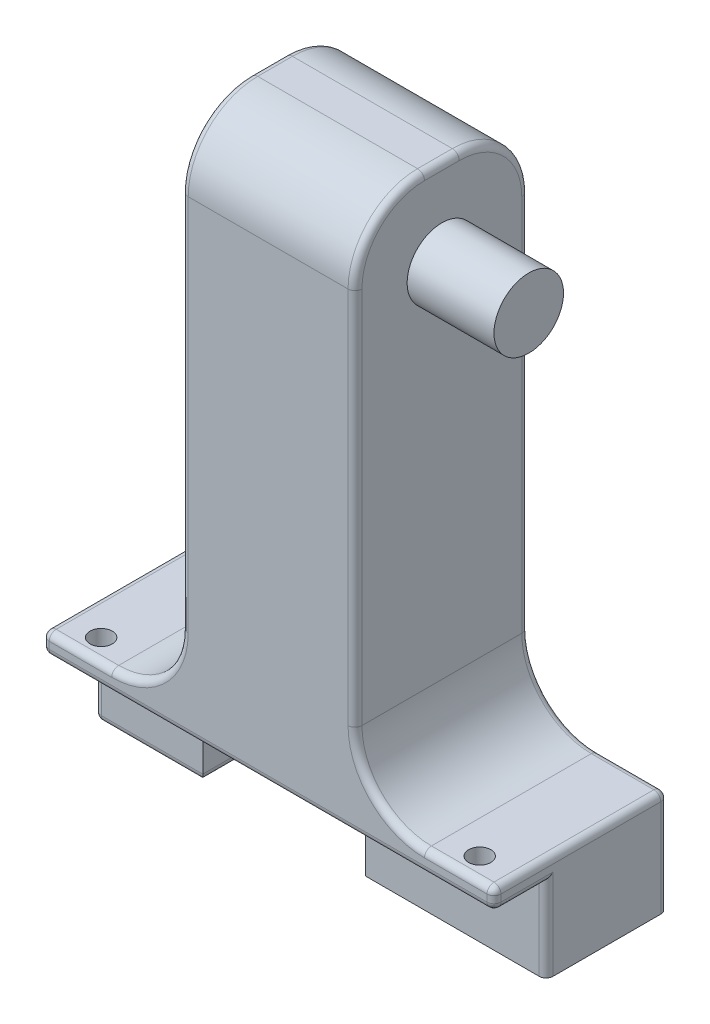
SolidWorks part; units mm, degrees
ref_plane "Front Plane" through (0, 0, 0) normal (0, 0, 1) x (1, 0, 0)
ref_plane "Top Plane" through (0, 0, 0) normal (0, 1, 0) x (1, 0, 0)
ref_plane "Right Plane" through (0, 0, 0) normal (1, 0, 0) x (0, 0, -1)
sketch "Sketch2" plane through (0, 0, 0) normal (0, 1, 0) x (1, 0, 0)
  line L1 (-32.5, -12.5) -> (32.5, -12.5)
  line L2 (-32.5, -12.5) -> (-32.5, 12.5)
  line L3 (-32.5, 12.5) -> (32.5, 12.5)
  line L4 (32.5, -12.5) -> (32.5, 12.5)
  line L5 (-32.5, -12.5) -> (32.5, 12.5) construction
  line L6 (-32.5, 12.5) -> (32.5, -12.5) construction
  point P0 (0, 0)
  dimension "D1" = 65
  dimension "D2" = 25
extrude "Boss-Extrude1" add sketch "Sketch2" along normal blind 3
sketch "Sketch3" plane through (0, 0, 0) normal (0, -1, 0) x (1, 0, 0)
  line L0 (32.5, -12.5) -> (-32.5, -12.5) construction
  line L1 (-32.5, 5) -> (-16.9, 5)
  line L2 (-32.5, 5) -> (-32.5, -12.5)
  line L3 (-32.5, -12.5) -> (-16.9, -12.5)
  line L4 (-16.9, 5) -> (-16.9, -12.5)
  line L10 (32.5, 5) -> (6.5, 5)
  line L12 (6.5, 5) -> (6.5, 0)
  line L13 (6.5, 0) -> (12.5, 0)
  line L14 (12.5, 0) -> (12.5, -12.5)
  line L15 (32.5, -12.5) -> (-32.5, -12.5) construction
  line L16 (12.5, -12.5) -> (32.5, -12.5)
  line L17 (32.5, -12.5) -> (32.5, 5)
  line L18 (-32.5, -12.5) -> (-32.5, 12.5) construction
  point P16 (0, 0)
  dimension "D1" = 15.6
  dimension "D2" = 26
  dimension "D3" = 20
  dimension "D4" = 17.5
extrude "Boss-Extrude2" add sketch "Sketch3" along normal blind 12
sketch "Sketch5" plane through (0, 3, 0) normal (0, 1, 0) x (1, 0, 0)
  circle A0 centre (27.2349, -9.2897) radius 1.6
  circle A1 centre (-27.2349, -9.2897) radius 1.6
  circle A2 centre (27.2349, -9.2897) radius 1.6 construction
extrude "Cut-Extrude1" cut sketch "Sketch5" against normal through all
sketch "Sketch6" plane through (0, 3, 0) normal (0, 1, 0) x (1, 0, 0)
  line L0 (-32.5, -12.5) -> (32.5, -12.5) construction
  line L1 (12.5, -12.5) -> (-12.5, -12.5)
  line L2 (12.5, -12.5) -> (12.5, 12.5)
  line L3 (12.5, 12.5) -> (-12.5, 12.5)
  line L4 (-12.5, -12.5) -> (-12.5, 12.5)
  line L5 (32.5, 12.5) -> (-32.5, 12.5) construction
  line L6 (0, -20.7065) -> (0, 20.7065) construction
  point P12 (0, 0)
  dimension "D1" = 25
extrude "Boss-Extrude3" add sketch "Sketch6" along normal blind 74.4
sketch "Sketch7" plane through (12.5, 0, 0) normal (1, 0, 0) x (0, 0, -1)
  line L0 (12.5, 77.4) -> (12.5, 3) construction
  line L1 (-12.5, 77.4) -> (12.5, 77.4) construction
  line L2 (-12.5, 77.4) -> (-12.5, 3) construction
  circle A0 centre (0, 64.9) radius 12.5
sketch "Sketch8" plane through (-12.5, 0, 0) normal (-1, 0, 0) x (0, 0, 1)
  circle A0 centre (0, 64.9) radius 12.5 construction
  circle A1 centre (0, 64.9) radius 12.5
ref_axis "Axis1" through (-18.9714, 64.9, 0) along (1, 0, 0)
fillet "Fillet1" radius 10 4 edges at (0, 77.4, 12.5) (0, 77.4, -12.5) (-12.5, 3, 0) (12.5, 3, 0)
fillet "Fillet2" radius 1 33 edges at (27.5, 3, 12.5) (15.4289, 5.9289, 12.5) (12.5, 40.2, 12.5) (12.5, 74.4711, 9.5711) (12.5, 77.4, 0) (12.5, 74.4711, -9.5711) (12.5, 40.2, -12.5) (15.4289, 5.9289, -12.5) (-27.5, 3, 12.5) (-15.4289, 5.9289, 12.5) (-12.5, 40.2, 12.5) (-12.5, 74.4711, 9.5711) (-12.5, 77.4, 0) (-12.5, 74.4711, -9.5711) (-27.5, 3, -12.5) (-15.4289, 5.9289, -12.5) (-24.7, -12, 5) (-16.9, -12, -3.75) (-24.7, -12, -12.5) (-32.5, -12, -3.75) (-32.5, 1.5, 12.5) (-32.5, -6, 5) (-32.5, 0, 8.75) (32.5, 1.5, 12.5) (32.5, -6, 5) (32.5, 0, 8.75) (0, 0, 12.5) (-32.5, -4.5, -12.5) (-32.5, 3, 0) (32.5, 3, 0) (32.5, -4.5, -12.5) (27.5, 3, -12.5) (-12.5, 40.2, -12.5)
sketch "Sketch9" plane through (12.5, 0, 0) normal (1, 0, 0) x (0, 0, -1)
  circle A0 centre (0, 64.9) radius 5
  dimension "D1" = 10
extrude "Boss-Extrude4" add sketch "Sketch9" along normal blind 12.5
